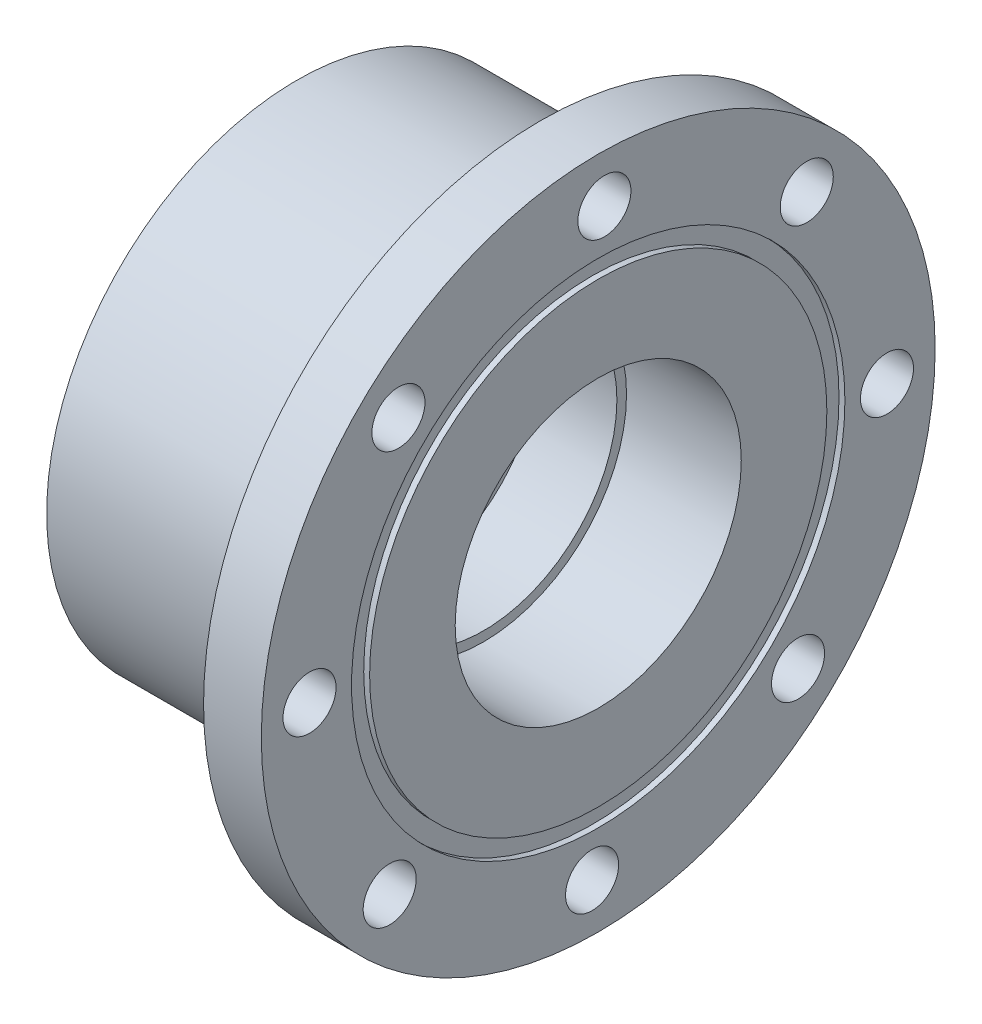
SolidWorks part; units mm, degrees
ref_plane "Front Plane" through (0, 0, 0) normal (0, 0, 1) x (1, 0, 0)
ref_plane "Top Plane" through (0, 0, 0) normal (0, 1, 0) x (1, 0, 0)
ref_plane "Right Plane" through (0, 0, 0) normal (1, 0, 0) x (0, 0, -1)
sketch "Main sketch" plane through (0, 0, 0) normal (0, 0, 1) x (1, 0, 0)
  line L0 (0, 9) -> (0, 19.995)
  line L1 (0, 19.995) -> (-8, 19.995)
  line L2 (-8, 19.995) -> (-8, 33.02)
  line L3 (-8, 33.02) -> (24.13, 33.02)
  line L4 (24.13, 33.02) -> (24.13, 44.45)
  line L5 (24.13, 44.45) -> (31.75, 44.45)
  line L6 (31.75, 44.45) -> (31.75, 32.5438)
  line L7 (31.75, 32.5438) -> (30.9721, 32.5438)
  line L8 (30.9721, 32.5438) -> (30.9721, 30.1625)
  line L9 (30.9721, 30.1625) -> (31.75, 30.1625)
  line L10 (31.75, 30.1625) -> (31.75, 18.8722)
  line L11 (31.75, 18.8722) -> (16.6116, 18.8722)
  line L12 (16.6116, 18.8722) -> (16.6116, 17.6022)
  line L13 (16.6116, 17.6022) -> (6.35, 17.6022)
  line L14 (6.35, 17.6022) -> (6.35, 9)
  line L15 (6.35, 9) -> (0, 9)
  line L16 (0, 0) -> (0, 9) construction
  dimension "D1" = 9
  dimension "D2" = 19.995
  dimension "D3" = 25.4
  dimension "D4" = 17.6022
  dimension "D5" = 8
  dimension "D6" = 44.45
  dimension "D7" = 18.8722
  dimension "D8" = 32.5437
  dimension "D11" = 6.35
  dimension "D12" = 10.2616
  dimension "D13" = 33.02
  dimension "D14" = 7.62
  dimension "D9" = 30.1625
  dimension "D10" = 0.7779
ref_axis "Axis1" through (71.9501, 0, 0) along (-1, 0, 0)
revolve "Revolve1" add sketch "Main sketch" angle 360 about axis through (71.9501, 0, 0) along (-1, 0, 0)
sketch "Sketch2" plane through (31.75, 0, 0) normal (1, 0, 0) x (0, 0, -1)
  circle A0 centre (0, 0) radius 38.1 construction
  point P0 (0, 0)
  point P3 (-38.0913, 0.8131)
  point P4 (-27.5096, -26.3597)
  point P7 (-0.8131, -38.0913)
  point P8 (26.3597, -27.5096)
  point P9 (38.0913, -0.8131)
  point P10 (27.5096, 26.3597)
  point P11 (0.8131, 38.0913)
  point P12 (-26.3597, 27.5096)
  point P13 (0, 0)
  point P16 (0, 0)
  dimension "D2" = 76.2
  dimension "D1" = 8
hole_wizard "M6 Clearance Hole1" positions "Sketch2" profile "Sketch3" hole size "M6" standard "ISO" end condition through all
sketch "Sketch3" plane through (31.75, 0, 0) normal (0, 1, 0) x (0, 0, -1)
  line L0 (0, 0) -> (0, 39.75)
  line L1 (0, 39.75) -> (3.5, 39.75)
  line L2 (3.5, 39.75) -> (3.5, 0)
  line L5 (3.5, 0) -> (0, 0)
  line L11 (0, -6.35) -> (0, 107.95) construction
  dimension "Thru Hole Dia." = 7
  dimension "Thru Hole Depth" = 39.75
equation "\"Shaft_OD\"= 17mm"
equation "\"O_Ring_ID\"= 2.375in"
equation "\"O_Ring_CS\"= 1 / 16in'cross section"
equation "\"Bearing_OD\" = 39.99mm"
equation "\"Bearing_Depth\" = 8mm"
equation "\"Stationary_Face_Seal_OD\"= 1.386in"
equation "\"Flange_Dia\"= 3.5in"
equation "\"Screw_Dia\"= 6mm"
equation "\"Screws\"= 8"
equation "\"Seal_Space\"= 1in"
equation "\"D1@Main sketch\"=\"Shaft_OD\" / 2 + .5mm"
equation "\"D2@Main sketch\" = \"Bearing_OD\" / 2"
equation "\"D3@Main sketch\" = \"Seal_Space\""
equation "\"D4@Main sketch\" = \"Stationary_Face_Seal_OD\" / 2"
equation "\"D5@Main sketch\" = \"Bearing_Depth\""
equation "\"D6@Main sketch\" = \"Flange_Dia\" / 2"
equation "\"Seal_Area_Dia\" = 37mm"
equation "\"D7@Main sketch\" =  ( \"Stationary_Face_Seal_OD\" / 2 )  + .05in"
equation "\"D8@Main sketch\"=\"O_Ring_ID\" / 2 + \"O_Ring_CS\" * 1.5"
equation "\"Face_Seal_Height\"=0.404"
equation "\"D12@Main sketch\" = \"Face_Seal_Height\""
equation "\"Housing_OR\"= 1.3"
equation "\"D13@Main sketch\"=\"Housing_OR\""
equation "\"D10@Main sketch\"=\"O_Ring_CS\"*.49"
equation "\"D9@Main sketch\"=\"O_Ring_ID\"/2"
equation "\"D2@Sketch2\"=\"Flange_Dia\"-.50"
